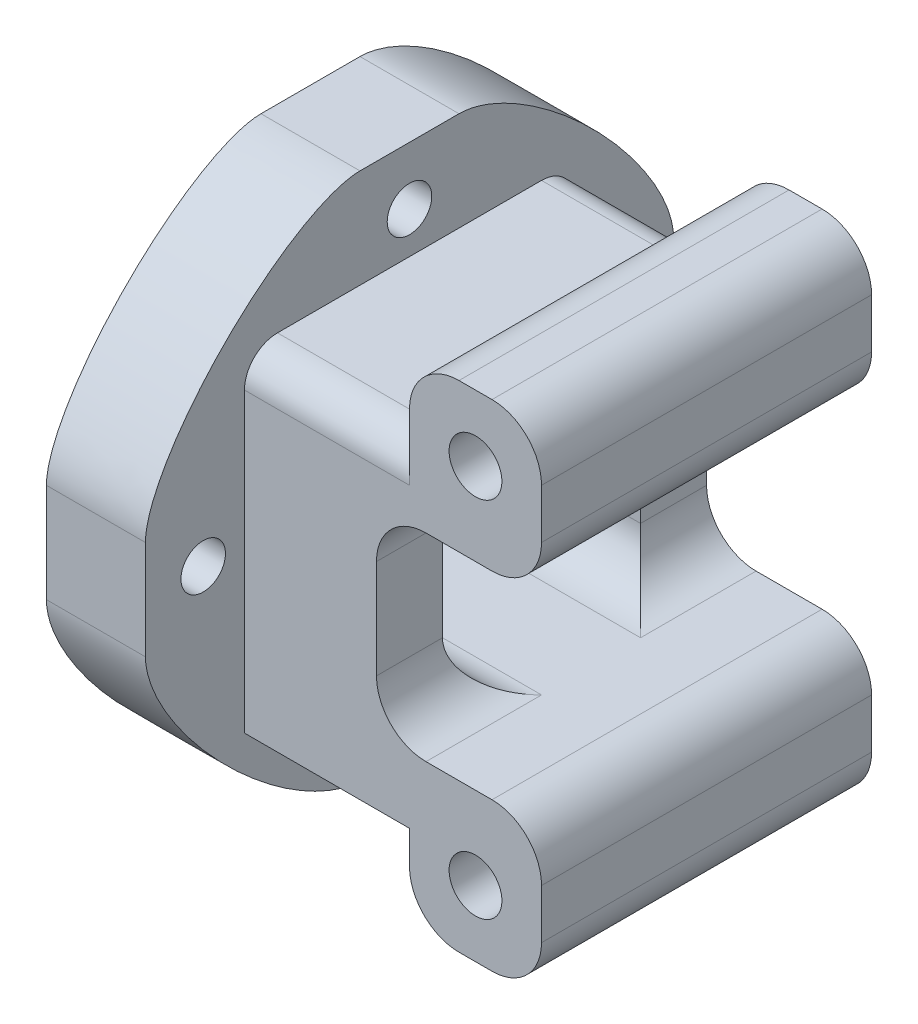
SolidWorks part; units mm, degrees
ref_plane "Front" through (0, 0, 0) normal (0, 0, 1) x (1, 0, 0)
ref_plane "Top" through (0, 0, 0) normal (0, 1, 0) x (1, 0, 0)
ref_plane "Right" through (0, 0, 0) normal (1, 0, 0) x (0, 0, -1)
sketch "Sketch1" plane through (0, 0, 0) normal (1, 0, 0) x (0, 0, -1)
  line L1 (0, 0) -> (-20, 0)
  line L2 (0, 0) -> (0, -20)
  line L3 (0, -20) -> (-20, -20)
  line L4 (-20, 0) -> (-20, -20)
  dimension "D1" = 20
  dimension "D2" = 20
extrude "Boss-Extrude1" add sketch "Sketch1" along normal blind 4
sketch "Sketch2" plane through (4, 0, 0) normal (1, 0, 0) x (0, 0, -1)
  line L0 (0, -20) -> (0, 0) construction
  line L1 (-20, -20) -> (0, -20) construction
  circle A0 centre (-10, -10) radius 3.65
  dimension "D1" = 7.3
  dimension "D2" = 10
  dimension "D3" = 10
extrude "Cut-Extrude1" cut sketch "Sketch2" against normal blind 2.5
sketch "Sketch3" plane through (1.5, 0, 0) normal (1, 0, 0) x (0, 0, -1)
  circle A0 centre (-10, -10) radius 2.25
  dimension "D1" = 4.5
extrude "Cut-Extrude2" cut sketch "Sketch3" against normal through all
sketch "Sketch4" plane through (4, 0, 0) normal (1, 0, 0) x (0, 0, -1)
  line L0 (0, 0) -> (-20, 0) construction
  line L1 (-20, -20) -> (-16, -20)
  line L2 (-20, -20) -> (-20, 0)
  line L3 (-20, 0) -> (-16, 0)
  line L4 (-16, -20) -> (-16, 0)
  line L5 (0, -20) -> (0, 0) construction
  line L6 (-16, 0) -> (0, 0)
  line L7 (-16, 0) -> (-16, -4)
  line L8 (-16, -4) -> (0, -4)
  line L9 (0, 0) -> (0, -4)
  line L10 (-20, -20) -> (0, -20) construction
  line L11 (0, -4) -> (-4, -4)
  line L12 (0, -4) -> (0, -20)
  line L13 (0, -20) -> (-4, -20)
  line L14 (-4, -4) -> (-4, -20)
  line L16 (-4, -20) -> (-16, -20)
  line L17 (-4, -20) -> (-4, -16)
  line L18 (-4, -16) -> (-16, -16)
  line L19 (-16, -20) -> (-16, -16)
  line M6 (0, -20) -> (0, 0)
  line M7 (0, 0) -> (-20, 0)
  line M8 (-20, 0) -> (-20, -20)
  line M9 (-20, -20) -> (0, -20)
  dimension "D1" = 4
  dimension "D2" = 4
  dimension "D3" = 4
  dimension "D4" = 4
extrude "Boss-Extrude2" add sketch "Sketch4" along normal blind 10 contours L4 M9 M7 M8 | L14 L18 L4 M9 | L8 L14 M9 M6 | L4 L8 M6 M7 region at (4, -10, 18) region at (4, -18, 10) region at (4, -12, 2) region at (4, -2, 8)
sketch "Sketch7" plane through (14, 0, 0) normal (1, 0, 0) x (0, 0, -1)
  line L0 (-20, 0) -> (-20, -20) construction
  line L1 (0, -20) -> (-20, -20)
  line L2 (0, -20) -> (0, -16)
  line L3 (0, -16) -> (-20, -16)
  line L4 (-20, -20) -> (-20, -16)
  line L6 (0, 0) -> (-20, 0)
  line L7 (0, 0) -> (0, -4)
  line L8 (0, -4) -> (-20, -4)
  line L9 (-20, 0) -> (-20, -4)
  dimension "D1" = 4
  dimension "D2" = 4
extrude "Boss-Extrude3" add sketch "Sketch7" along normal blind 10
sketch "Sketch8" plane through (0, -20, 0) normal (0, -1, 0) x (-1, 0, 0)
  line L0 (-24, -20) -> (0, -20) construction
  line L1 (-24, 0) -> (-16, 0)
  line L2 (-24, 0) -> (-24, -20)
  line L3 (-24, -20) -> (-16, -20)
  line L4 (-16, 0) -> (-16, -20)
  dimension "D1" = 8
extrude "Boss-Extrude4" add sketch "Sketch8" along normal blind 5
sketch "Sketch9" plane through (0, 0, 0) normal (0, 1, 0) x (1, 0, 0)
  line L0 (24, -20) -> (0, -20) construction
  line L1 (24, 0) -> (16, 0)
  line L2 (24, 0) -> (24, -20)
  line L3 (24, -20) -> (16, -20)
  line L4 (16, 0) -> (16, -20)
  dimension "D1" = 8
extrude "Boss-Extrude5" add sketch "Sketch9" along normal blind 5
sketch "Sketch10" plane through (0, 0, 0) normal (0, 0, -1) x (-1, 0, 0)
  line L0 (-24, -4) -> (-14, -4) construction
  line L1 (-24, -4) -> (-24, 5) construction
  circle A0 centre (-20, 1) radius 1.6
  circle A1 centre (-20, -21) radius 1.6
  dimension "D1" = 3.2
  dimension "D2" = 5
  dimension "D3" = 4
  dimension "D4" = 2
extrude "Cut-Extrude5" cut sketch "Sketch10" against normal through all
sketch "Sketch11" plane through (0, 0, 0) normal (-1, 0, 0) x (0, 0, 1)
  line L0 (0, -20) -> (0, 0) construction
  line L1 (-6, 6) -> (26, 6)
  line L2 (-6, 6) -> (-6, -26)
  line L3 (-6, -26) -> (26, -26)
  line L4 (26, 6) -> (26, -26)
  line L5 (0, 0) -> (20, 0) construction
  line L7 (20, -20) -> (0, -20)
  line L8 (20, -20) -> (20, 0)
  line L9 (20, 0) -> (0, 0)
  line L10 (0, -20) -> (0, 0)
  line M4 (0, 0) -> (0, -20)
  line M5 (0, -20) -> (20, -20)
  line M6 (20, -20) -> (20, 0)
  line M7 (20, 0) -> (0, 0)
  dimension "D1" = 32
  dimension "D2" = 32
  dimension "D3" = 6
  dimension "D4" = 6
extrude "Boss-Extrude6" add sketch "Sketch11" against normal blind 6 contours L4 L1 L2 L3 M4 M7 M6 M5 region at (0, 5.5475, 10)
fillet "Fillet6" radius 3 6 edges at (16, 5, 10) (24, 5, 10) (24, -4, 10) (16, -25, 10) (24, -16, 10) (24, -25, 10)
sketch "Sketch13" plane through (0, 0, 0) normal (-1, 0, 0) x (0, 0, 1)
  line L0 (-6, -26) -> (26, -26) construction
  line L1 (26, 6) -> (26, -26) construction
  line L2 (-6, 6) -> (26, 6) construction
  line L3 (-6, 6) -> (-6, -26) construction
  circle A0 centre (22.5, -10) radius 1.35
  circle A1 centre (10, 2.5) radius 1.35
  circle A2 centre (-2.5, -10) radius 1.35
  circle A3 centre (10, -22.5) radius 1.35
  dimension "D1" = 2.7
  dimension "D2" = 2.7
  dimension "D3" = 2.7
  dimension "D4" = 2.7
  dimension "D5" = 3.5
  dimension "D6" = 3.5
  dimension "D7" = 3.5
  dimension "D8" = 3.5
extrude "Cut-Extrude7" cut sketch "Sketch13" against normal blind 6
fillet "Fillet7" radius 3 8 edges at (14, -16, 2) (14, -16, 18) (14, -4, 18) (14, -4, 2) (9, -16, 4) (9, -16, 16) (9, -4, 4) (9, -4, 16)
fillet "Fillet13" radius 2 2 edges at (11, 0, 20) (11, 0, 0)
fillet "Fillet14" radius 13 4 edges at (3, -26, -6) (3, 6, -6) (3, -26, 26) (3, 6, 26) conic rho 0.25
